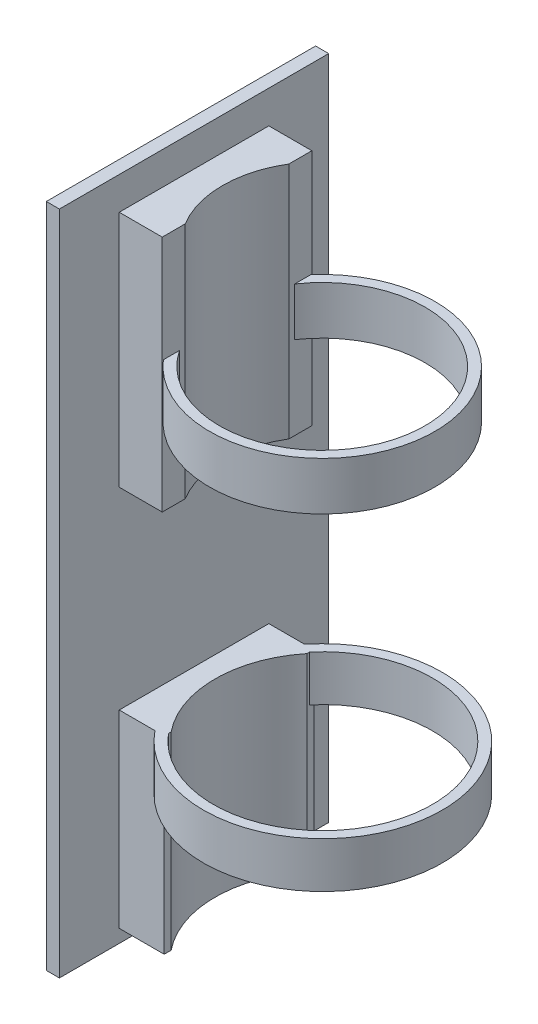
SolidWorks part; units mm, degrees
ref_plane "Front Plane" through (0, 0, 0) normal (0, 0, 1) x (1, 0, 0)
ref_plane "Top Plane" through (0, 0, 0) normal (0, 1, 0) x (1, 0, 0)
ref_plane "Right Plane" through (0, 0, 0) normal (1, 0, 0) x (0, 0, -1)
sketch "Sketch1" plane through (0, 0, 0) normal (0, 0, 1) x (1, 0, 0)
  line L0 (-35.4738, -26.6959) -> (-35.4738, 75.0669)
  line L1 (-35.4738, 75.0669) -> (-37.4738, 75.0669)
  line L2 (-37.4738, 75.0669) -> (-37.4738, -26.6959)
  line L3 (-35.4738, -26.6959) -> (-37.4738, -26.6959)
  line L4 (15.0549, -120.6448) -> (-35.4738, -120.6448) construction
  line L5 (-35.4738, -120.6448) -> (14.9683, -69.9449) construction
  line L6 (14.9683, -69.9449) -> (-35.4738, -69.9449) construction
  line L7 (15.0549, -120.6448) -> (25.118, -120.6806) construction
  line L9 (-35.4738, -24.6959) -> (-28.6071, -24.6959)
  line L10 (-35.4738, -24.6959) -> (-35.4738, 4.1976)
  line L11 (-35.4738, 4.1976) -> (-28.6071, 4.1976)
  line L12 (-28.6071, -24.6959) -> (-28.6071, 4.1976)
  line L14 (-35.4738, 33.6794) -> (-28.9025, 33.6794)
  line L15 (-35.4738, 33.6794) -> (-35.4738, 70.0669)
  line L16 (-35.4738, 70.0669) -> (-28.9025, 70.0669)
  line L17 (-28.9025, 33.6794) -> (-28.9025, 70.0669)
  line L19 (7.4905, -116.3114) -> (-35.4738, -116.3114)
  line L20 (7.4905, -116.3114) -> (7.4905, -73.2509)
  line L21 (7.4905, -73.2509) -> (-35.4738, -73.2509)
  line L22 (-35.4738, -116.3114) -> (-35.4738, -73.2509)
  line L23 (25.118, -120.6806) -> (25.118, -69.9449) construction
  circle A0 centre (25.118, -120.6806) radius 2.25
  circle A1 centre (15.0549, -120.6448) radius 2.25
  circle A2 centre (25.118, -69.9449) radius 2.25
  circle A3 centre (14.9683, -69.9449) radius 2.25
  point P26 (0, 0)
  point P27 (0, 0)
  dimension "D1" = 4.5
  dimension "D2" = 4.5
  dimension "D3" = 4.5
  dimension "D4" = 4.5
  dimension "D5" = 2
  dimension "D6" = 28.8936
  dimension "D7" = 2
  dimension "D8" = 5
extrude "Boss-Extrude1" add sketch "Sketch1" along normal mid plane 22.86 contours L9 L12 L11 L0 | L14 L17 L16 L0 region at (-32.0405, -10.2492, 0) region at (-32.1881, 51.8732, 0)
extrude "Boss-Extrude2" add sketch "Sketch1<3>" along normal mid plane 41.148 contours L3 L0 L1 L2 region at (-36.4738, 24.1855, 0)
sketch "Sketch1<3>" plane through (0, 0, 0) normal (0, 0, 1) x (1, 0, 0) same geometry as "Sketch1"
sketch "Sketch2" plane through (0, -24.6959, 0) normal (0, -1, 0) x (1, 0, 0)
  line L0 (-32.2738, 0) -> (0.7262, 0) construction
  line L2 (-37.4738, 20.574) -> (-37.4738, -20.574) construction
  circle A0 centre (-15.7738, 0) radius 16.5
  point P5 (-14.9215, 0)
  dimension "D1" = 33
  dimension "D2" = 21.7
extrude "Cut-Extrude1" cut sketch "Sketch2" against normal up to next and the other way blind 35.052 contours A0
sketch "Sketch3" plane through (0, 33.6794, 0) normal (0, -1, 0) x (1, 0, 0)
  line L0 (-37.4738, 0) -> (21.8498, 0) construction
  line L1 (-37.4738, 20.574) -> (-37.4738, -20.574) construction
  circle A1 centre (-15.8838, 0) radius 15.24
  line M14 (-28.9025, -11.43) -> (-28.9025, 11.43)
  dimension "D1" = 30.48
  dimension "D3" = 21.59
extrude "Cut-Extrude4" cut sketch "Sketch3" against normal up to next contours L0 A1 M14 | L0 A1 M14 | L0 A1 M14 | A1 L0 M14 region at (-29.7968, 33.6794, 3.0023) region at (-29.7968, 33.6794, -3.0023) region at (-15.4141, 33.6794, 6.5851) region at (-15.4141, 33.6794, -6.5851)
sketch "Sketch15" plane through (0, 33.6794, 0) normal (0, -1, 0) x (1, 0, 0)
  line L0 (-37.4738, 20.574) -> (-37.4738, -20.574) construction
  circle A0 centre (-15.8838, 0) radius 15.715
  circle A1 centre (-15.8838, 0) radius 17.215
  dimension "D1" = 31.43
  dimension "D3" = 1.5
  dimension "D2" = 21.59
extrude "Boss-Extrude6" add sketch "Sketch15" against normal blind 7.366 from offset 12.7 offset against normal yes
sketch "Sketch16" plane through (0, 4.1976, 0) normal (0, 1, 0) x (1, 0, 0)
  line L0 (-37.4738, -20.574) -> (-37.4738, 20.574) construction
  circle A0 centre (-15.7877, 0) radius 16.75
  circle A1 centre (-15.7877, 0) radius 18.25
  dimension "D1" = 33.5
  dimension "D3" = 1.5
  dimension "D2" = 21.6861
extrude "Boss-Extrude7" add sketch "Sketch16" against normal blind 7
equation "\"hole\"=0.177165"
